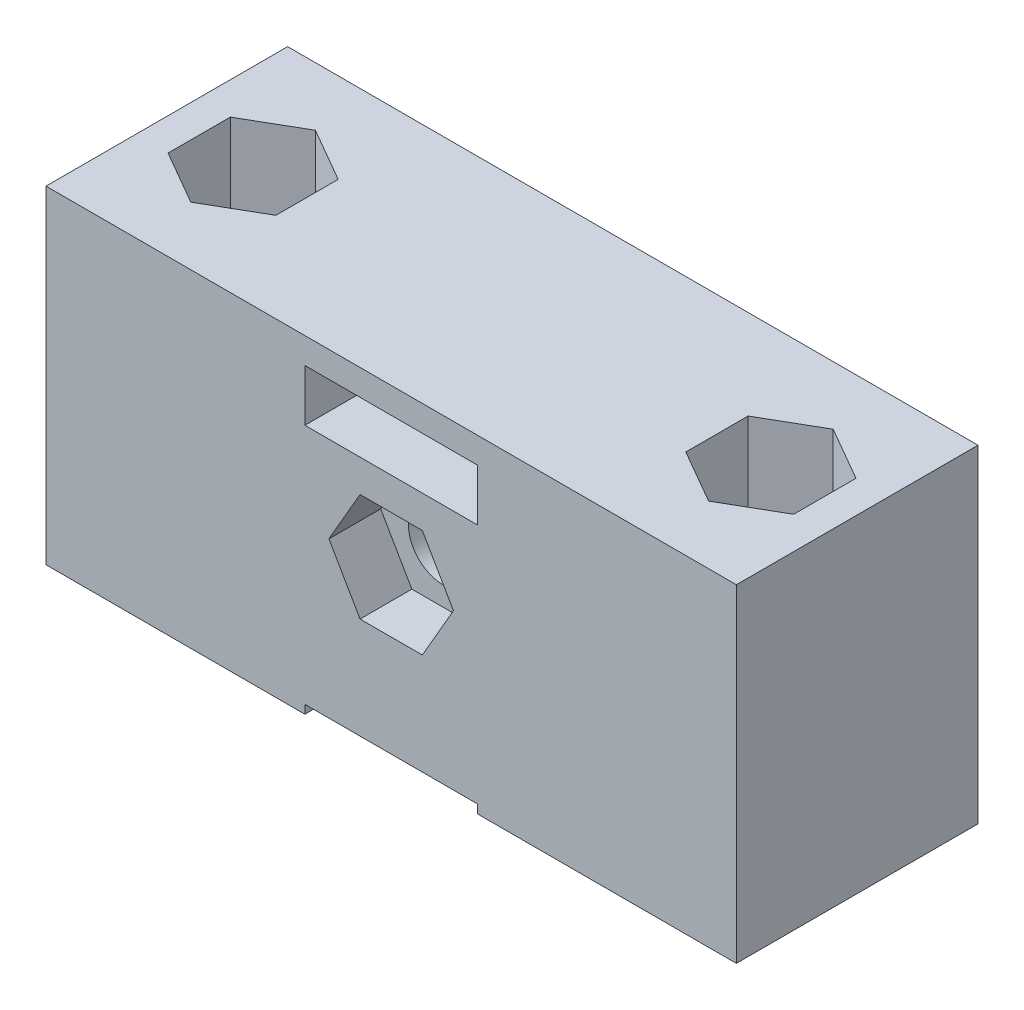
SolidWorks part; units mm, degrees
ref_plane "Front Plane" through (0, 0, 0) normal (0, 0, 1) x (1, 0, 0)
ref_plane "Top Plane" through (0, 0, 0) normal (0, 1, 0) x (1, 0, 0)
ref_plane "Right Plane" through (0, 0, 0) normal (1, 0, 0) x (0, 0, -1)
sketch "Sketch1" plane through (0, 0, 0) normal (0, 1, 0) x (1, 0, 0)
  line L1 (-20, 7) -> (20, 7)
  line L2 (-20, 7) -> (-20, -7)
  line L3 (-20, -7) -> (20, -7)
  line L4 (20, 7) -> (20, -7)
  line L5 (-20, 7) -> (20, -7) construction
  line L6 (-20, -7) -> (20, 7) construction
  point P0 (0, 0)
  dimension "D1" = 40
  dimension "D2" = 14
extrude "Boss-Extrude1" add sketch "Sketch1" along normal blind 19
sketch "Sketch2" plane through (0, 0, 7) normal (0, 0, 1) x (1, 0, 0)
  line L0 (0, 19) -> (0, 0) construction
  line L1 (-20, 19) -> (20, 19) construction
  line L3 (-5, 14.5) -> (5, 14.5)
  line L4 (-5, 14.5) -> (-5, 17.5)
  line L5 (-5, 17.5) -> (5, 17.5)
  line L6 (5, 14.5) -> (5, 17.5)
  line L7 (-5, 14.5) -> (5, 17.5) construction
  line L8 (-5, 17.5) -> (5, 14.5) construction
  line L9 (-5, -0.5) -> (5, -0.5)
  line L10 (-5, -0.5) -> (-5, 0.5)
  line L11 (-5, 0.5) -> (5, 0.5)
  line L12 (5, -0.5) -> (5, 0.5)
  line L13 (-5, -0.5) -> (5, 0.5) construction
  line L14 (-5, 0.5) -> (5, -0.5) construction
  point P5 (0, 16)
  dimension "D1" = 10
  dimension "D2" = 3
  dimension "D3" = 16
  dimension "D4" = 10
  dimension "D5" = 1
extrude "Cut-Extrude1" cut sketch "Sketch2" against normal blind 30
sketch "Sketch3" plane through (0, 0, 7) normal (0, 0, 1) x (1, 0, 0)
  line L0 (0, 19) -> (0, 0) construction
  line L1 (-20, 19) -> (20, 19) construction
  circle A0 centre (0, 9.5) radius 2
  dimension "D1" = 4
extrude "Cut-Extrude2" cut sketch "Sketch3" against normal through all
sketch "Sketch4" plane through (0, 19, 0) normal (0, 1, 0) x (1, 0, 0)
  line L0 (-20, 0) -> (20, 0) construction
  line L1 (-20, 7) -> (-20, -7) construction
  line L2 (20, -7) -> (20, 7) construction
  line L3 (0, 7) -> (0, -7) construction
  line L4 (20, 7) -> (-20, 7) construction
  line L5 (-20, -7) -> (20, -7) construction
  circle A0 centre (-15, 0) radius 1.6
  circle A1 centre (15, 0) radius 1.6
  dimension "D1" = 3.2
  dimension "D2" = 15
extrude "Cut-Extrude3" cut sketch "Sketch4" against normal through all
sketch "Sketch8" plane through (0, 0, 0) normal (0, -1, 0) x (-1, 0, 0)
  line L0 (-5, 7) -> (-5, -7) construction
  line L1 (5, -7) -> (-5, -7)
  line L2 (5, -7) -> (5, -6)
  line L3 (5, -6) -> (-5, -6)
  line L4 (-5, -7) -> (-5, -6)
  dimension "D1" = 1
extrude "Boss-Extrude2" [suppressed] add sketch "Sketch8" against normal up to next
sketch "Sketch9" plane through (0, 19, 0) normal (0, 1, 0) x (1, 0, 0)
  line L0 (0, 7) -> (0, -7) construction
  line L1 (-15, 3.6084) -> (-18.125, 1.8042)
  line L2 (-18.125, 1.8042) -> (-18.125, -1.8042)
  line L3 (-18.125, -1.8042) -> (-15, -3.6084)
  line L4 (-15, -3.6084) -> (-11.875, -1.8042)
  line L5 (-11.875, -1.8042) -> (-11.875, 1.8042)
  line L6 (-11.875, 1.8042) -> (-15, 3.6084)
  line L7 (20, 7) -> (-20, 7) construction
  line L8 (-20, -7) -> (20, -7) construction
  line L9 (11.875, 1.8042) -> (15, 3.6084)
  line L10 (11.875, -1.8042) -> (11.875, 1.8042)
  line L11 (15, -3.6084) -> (11.875, -1.8042)
  line L12 (18.125, -1.8042) -> (15, -3.6084)
  line L13 (18.125, 1.8042) -> (18.125, -1.8042)
  line L14 (15, 3.6084) -> (18.125, 1.8042)
  circle A0 centre (-15, 0) radius 3.125 construction
  circle A1 centre (15, 0) radius 3.125 construction
  dimension "D1" = 6.25
extrude "Cut-Extrude4" cut sketch "Sketch9" against normal blind 10
sketch "Sketch10" plane through (0, 0, 7) normal (0, 0, 1) x (1, 0, 0)
  line L1 (1.8042, 12.625) -> (-1.8042, 12.625)
  line L2 (-1.8042, 12.625) -> (-3.6084, 9.5)
  line L3 (-3.6084, 9.5) -> (-1.8042, 6.375)
  line L4 (-1.8042, 6.375) -> (1.8042, 6.375)
  line L5 (1.8042, 6.375) -> (3.6084, 9.5)
  line L6 (3.6084, 9.5) -> (1.8042, 12.625)
  circle A0 centre (0, 9.5) radius 3.125 construction
  dimension "D1" = 6.25
extrude "Cut-Extrude5" cut sketch "Sketch10" against normal blind 3
equation "\"X-ROD-SPACING\"=45"
equation "\"Y-ROD-SPACING\"=75"
equation "\"Z-ROD-SPACING\"=17.5"
equation "\"Y-BED-OFFSET\"=2"
equation "\"Y-BED-ROD-INSET\"=3.5"
equation "\"Y-BED-SCREW-SPACING\"=209"
equation "\"Y-BED-SCREW-CUTOUT-SLOT-HEIGHT\"=2"
equation "\"T-SLOT-NUT-FILLET-RADIUS\"=0.5"
equation "\"T-SLOT-SCREW-SHAFT-RADIUS\"=1.55"
equation "\"T-SLOT-SCREW-SHAFT-CUTOUT-LENGTH\"=11"
equation "\"T-SLOT-NUT-DEPTH\"=3.5"
equation "\"T-SLOT-NUT-WIDTH\"=2.85"
equation "\"T-SLOT-NUT-END-DISTANCE\"=8"
equation "\"ACRYLIC-THICKNESS\"=10"
equation "\"ACRYLIC-THICKNESS2\"=4.5"
equation "\"ACRYLIC-TAB-CUTOUT-SIZE\"=\"ACRYLIC-THICKNESS\"+\"ACRYLIC-TAB-TOLERANCE\"*2"
equation "\"ACRYLIC-TAB-TOLERANCE\"=-.05"
equation "\"ACRYLIC-TAB-WIDTH\"=\"ACRYLIC-THICKNESS\""
equation "\"ACRYLIC-M3-HOLE\"=2.9"
equation "\"SMOOTHROD-CAP-SCREW-DISTANCE\"=20"
equation "\"FRAME-WIDTH-INNER\"=370"
equation "\"NEMA17-HOLE-SPACING\"=31"
equation "\"NEMA17-CENTRAL-CUTOUT\"=22.5"
equation "\"Z-BRACKET-REACH\"=55"
equation "\"Z-ROD-INSET\"=13.5"
equation "\"TOP-BRACKET-SPACING\"=40"
equation "\"SMOOTHROD-X-LENGTH\"=350"
equation "\"SMOOTHROD-Y-LENGTH\"=350"
equation "\"SMOOTHROD-Z-LENGTH\"=350"
equation "\"SMOOTHROD-TIGHTENING-HEADROOM\"=.25"
equation "\"LEADSCREW-Z-LENGTH\"=300"
equation "\"SCREW-LENGTH-FRAME\"=\"ACRYLIC-THICKNESS\" + 10"
equation "\"SCREW-LENGTH-MOTOR\"=\"ACRYLIC-THICKNESS\" + 5"
equation "\"SCREW-LENGTH-EXTRUDER\"=28"
equation "\"SCREW-HEAD-RADIUS\"=6"
equation "\"PRINTED-M3-HOLE\"=3.5"
equation "\"PRINTED-X-SMOOTHROD-DIAMETER\"=8.8"
equation "\"PRINTED-X-SMOOTHROD-CUTOUT\"=10"
equation "\"PRINTED-X-BASE-HEIGHT\"=10"
equation "\"PRINTED-LM8UU-CUTOUT-SIZE\"=15.5"
equation "\"PRINTED-LM8UU-CUTOUT-LENGTH\"=24.5"
equation "\"PRINTED-X-IDLER-HEIGHT\"=16"
equation "\"PSU-MOUNTING-WIDTH\"=95"
equation "\"PSU-MOUNTING-HEIGHT\"=177"
equation "\"Y-BELT-TO-ROD-DISTANCE\"=20"
equation "\"SPOOL-HOLDER-ROD-SPACING\"=150"
equation "\"ACRYLIC-X-CARRIAGE-WIDTH\"=55"
equation "\"ACRYLIC-X-CARRIAGE-HEIGHT\"=75"
equation "\"ACRYLIC-X-CARRIAGE-LM8UU-CUTOUT-WIDTH\"=24.25"
equation "\"ACRYLIC-X-CARRIAGE-LM8UU-CUTOUT-HEIGHT\"=11.0"
equation "\"ACRYLIC-X-CARRIAGE-SCREW-SPACING-X\"=15"
equation "\"ACRYLIC-X-CARRIAGE-SCREW-SPACING-Y\"=33"
equation "\"ACRYLIC-X-CARRIAGE-CENTER-TAB-SPACING\"=14"
equation "\"ACRYLIC-X-CARRIAGE-EXTRUDER-OFFSET\"=26"
equation "\"ACRYLIC-X-CARRIAGE-EXTRUDER-ANGLE\"=90"
equation "\"ACRYLIC-X-CARRIAGE-EXTRUDER-SHELF-DEPTH\"=\"ACRYLIC-X-CARRIAGE-EXTRUDER-OFFSET\" + 28"
equation "\"ACRYLIC-X-CARRIAGE-EXTRUDER-BRACE-SPACING\"=23"
equation "\"ACRYLIC-X-CARRIAGE-EXTRUDER-BRACE-TAB-OFFSET\"=20"
equation "\"ACRYLIC-X-CARRIAGE-EXTRUDER-BRACE-HEIGHT\"=35"
equation "\"ACRYLIC-X-CARRIAGE-EXTRUDER-BRACE-SCREW-SPACING\"=22"
equation "\"ACRYLIC-X-CARRIAGE-DUAL-WIDTH-MULTIPLIER\"=1.65"
equation "\"ACRYLIC-X-CARRIAGE-DUAL-HOTEND-SPACING\"=42"
equation "\"ACRYLIC-X-CARRIAGE-DUAL-WIDTH\"=75"
equation "\"ACRYLIC-X-CARRIAGE-DUAL-HOTEND-SEPARATION\"=36"
equation "\"ACRYLIC-X-CARRIAGE-DUAL-MOUNT-PLATE-DEPTH\"=75"
equation "\"ACRYLIC-X-CARRIAGE-DUAL-MOUNT-BRACE-WIDTH\"=33"
equation "\"ACRYLIC-X-CARRIAGE-DUAL-MOUNT-SCREW-WIDTH\"=40"
equation "\"BLOWER-FAN-WIDTH\"=15"
equation "\"PRINTED-M3-NUT-AF\"=6.25"
equation "\"D1@Sketch9\"=\"PRINTED-M3-NUT-AF\""
equation "\"D1@Sketch10\"=\"PRINTED-M3-NUT-AF\""
